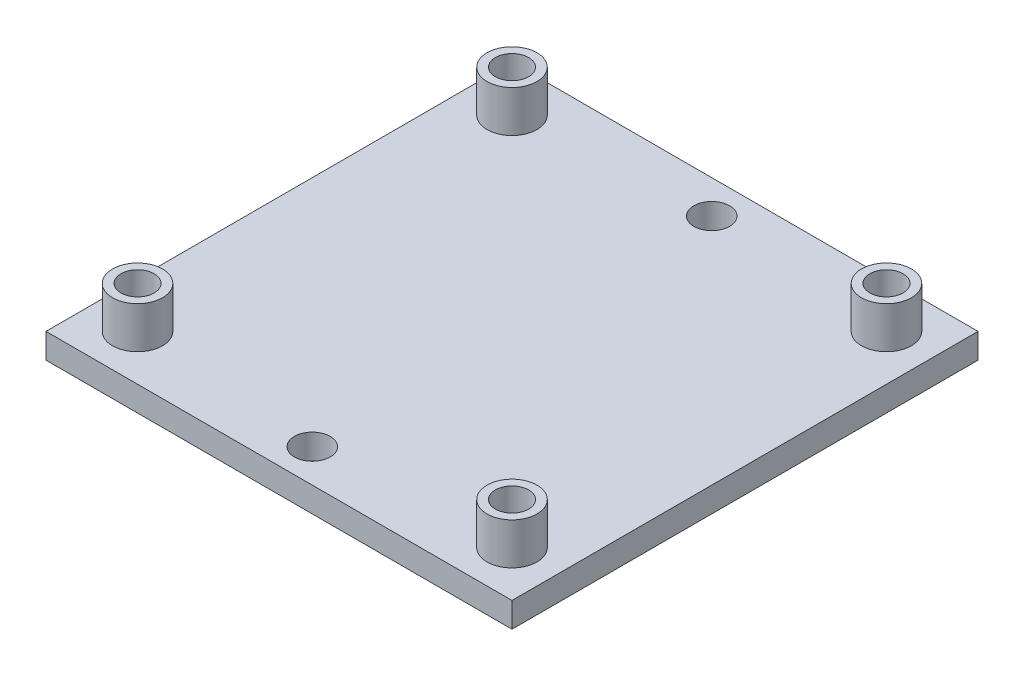
SolidWorks part; units mm, degrees
ref_plane "Front Plane" through (0, 0, 0) normal (0, 0, 1) x (1, 0, 0)
ref_plane "Top Plane" through (0, 0, 0) normal (0, 1, 0) x (1, 0, 0)
ref_plane "Right Plane" through (0, 0, 0) normal (1, 0, 0) x (0, 0, -1)
sketch "SK_Plate" plane through (0, 0, 0) normal (0, 1, 0) x (1, 0, 0)
  line L1 (-28, 28) -> (28, 28)
  line L2 (-28, 28) -> (-28, -28)
  line L3 (-28, -28) -> (28, -28)
  line L4 (28, 28) -> (28, -28)
  dimension "D1" = 56
  dimension "D2" = 56
  dimension "D3" = 28
  dimension "D4" = 28
extrude "EX_Plate" add sketch "SK_Plate" along normal blind 3
ref_plane "PL_Zp3" through (0, 3, 0) normal (0, 1, 0) x (1, 0, 0)
sketch "SK_Standoffs" plane through (0, 3, 0) normal (0, 1, 0) x (1, 0, 0)
  circle A0 centre (22.5, -22.5) radius 3
  circle A1 centre (-22.5, -22.5) radius 3
  circle A2 centre (22.5, 22.5) radius 3
  circle A3 centre (-22.5, 22.5) radius 3
  dimension "D3" = 6
  dimension "D6" = 6
  dimension "D9" = 6
  dimension "D12" = 6
  dimension "D1" = 22.5
  dimension "D2" = 22.5
  dimension "D4" = 22.5
  dimension "D5" = 22.5
  dimension "D7" = 22.5
  dimension "D8" = 22.5
  dimension "D10" = 22.5
  dimension "D11" = 22.5
extrude "EX_Standoffs" add sketch "SK_Standoffs" along normal blind 5
ref_plane "PL_Zp8" through (0, 8, 0) normal (0, 1, 0) x (1, 0, 0)
sketch "SK_Inserts_M3" plane through (0, 8, 0) normal (0, 1, 0) x (1, 0, 0)
  circle A0 centre (22.5, -22.5) radius 2
  circle A1 centre (-22.5, -22.5) radius 2
  circle A2 centre (22.5, 22.5) radius 2
  circle A3 centre (-22.5, 22.5) radius 2
  dimension "D3" = 4
  dimension "D6" = 4
  dimension "D9" = 4
  dimension "D12" = 4
  dimension "D1" = 22.5
  dimension "D2" = 22.5
  dimension "D4" = 22.5
  dimension "D5" = 22.5
  dimension "D7" = 22.5
  dimension "D8" = 22.5
  dimension "D10" = 22.5
  dimension "D11" = 22.5
extrude "CUT_Inserts_M3" cut sketch "SK_Inserts_M3" against normal blind 5.7
sketch "SK_PanHoles" plane through (0, 0, 0) normal (0, 1, 0) x (1, 0, 0)
  circle A0 centre (0, -24) radius 2.15
  circle A1 centre (0, 24) radius 2.15
  dimension "D2" = 4.3
  dimension "D4" = 4.3
  dimension "D1" = 24
  dimension "D3" = 24
extrude "CUT_PanHoles" cut sketch "SK_PanHoles" along normal blind 3
ref_axis "AX_X" through (0, 0, -30.8) along (0, 0, 1)
ref_axis "AX_Y" through (30.8, 0, 0) along (-1, 0, 0)
ref_axis "AX_Z" through (0, 8.4, 0) along (0, -1, 0)
sketch "SK_F_IF_Driver" plane through (0, 8, 0) normal (0, 1, 0) x (1, 0, 0)
  point P0 (0, 0)
